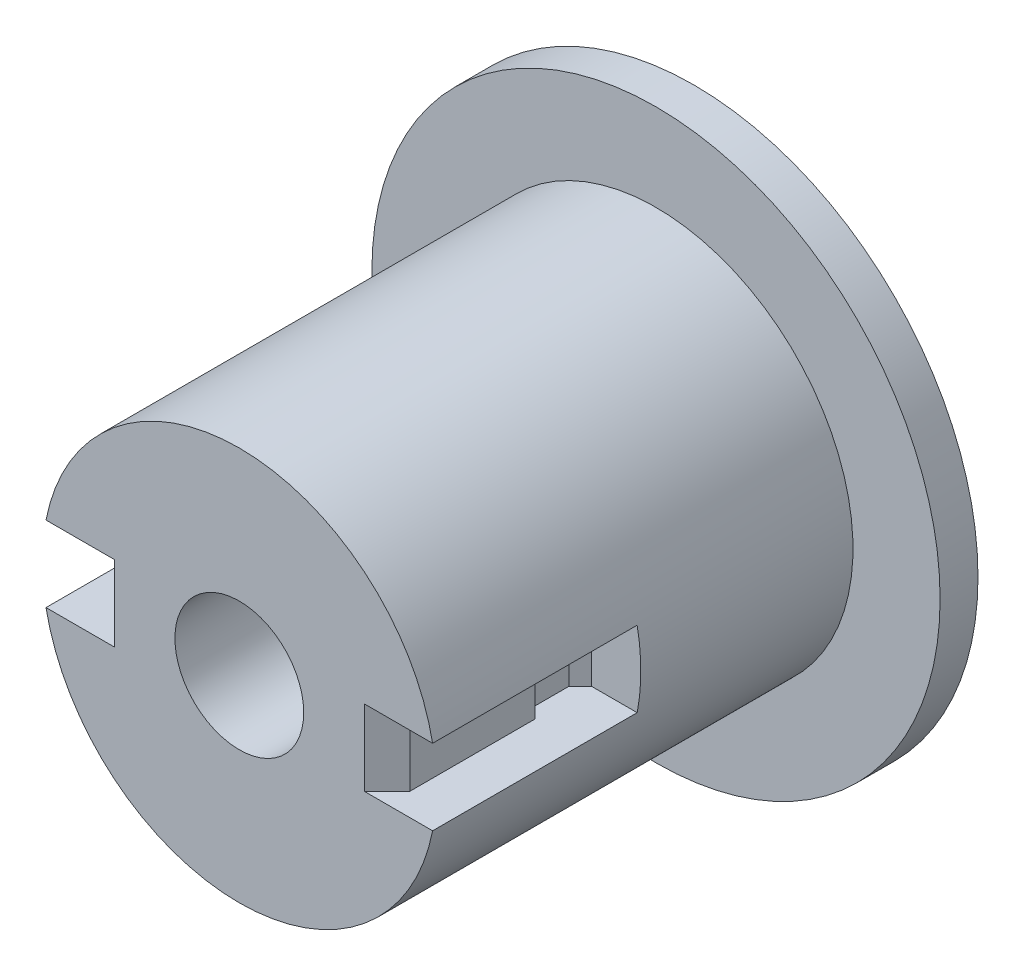
SolidWorks part; units mm, degrees
ref_plane "Front" through (0, 0, 0) normal (0, 0, 1) x (1, 0, 0)
ref_plane "Top" through (0, 0, 0) normal (0, 1, 0) x (1, 0, 0)
ref_plane "Right" through (0, 0, 0) normal (1, 0, 0) x (0, 0, -1)
sketch "Axle base sketch" plane through (0, 0, 0) normal (0, 0, 1) x (1, 0, 0)
  circle A0 centre (0, 0) radius 26
  dimension "D1" = 52
extrude "Axle" add sketch "Axle base sketch" along normal blind 55
sketch "Guard base sketch" plane through (0, 0, 0) normal (0, 0, -1) x (-1, 0, 0)
  circle A0 centre (0, 0) radius 37.5
  dimension "D1" = 75
extrude "Guard base" add sketch "Guard base sketch" along normal blind 5
sketch "Inner axle base sketch" plane through (0, 0, 55) normal (0, 0, 1) x (1, 0, 0)
  circle A0 centre (0, 0) radius 8.5
  dimension "D1" = 17
extrude "Inner axle hole" cut sketch "Inner axle base sketch" against normal through all
sketch "Coupling tooth base sketch" plane through (0, 0, 0) normal (0, 1, 0) x (1, 0, 0)
  line L0 (16.5, -55) -> (26, -55)
  line L1 (26, -55) -> (26, -28)
  line L2 (26, -55) -> (26, 0) construction
  line L3 (26, -28) -> (19.5, -28)
  line L5 (18, -34) -> (19.5, -35.5)
  line L6 (19.5, -35.5) -> (19.5, -52)
  line L7 (19.5, -52) -> (16.5, -55)
  line L9 (19.5, -28) -> (18, -29.5)
  line L10 (18, -29.5) -> (18, -34)
  dimension "D1" = 9.5
  dimension "D2" = 1.5
  dimension "D3" = 8
  dimension "D4" = 27
  dimension "D5" = 7.5
  dimension "D7" = 135
  dimension "D8" = 135
extrude "Coupling tooth room" cut sketch "Coupling tooth base sketch" against normal blind 5 and the other way blind 5 contours L9 L10 L5 L6 L7 L0 L1 L3 region at (22.4613, 0, 41.3333)
mirror "Coupling teeth" about plane through (0, 0, 0) normal (1, 0, 0) of "Coupling tooth room"
equation "\"53_55_spool_inner_diameter\"=53"
equation "\"D1@Axle base sketch\"=\"53_55_spool_inner_diameter\"-\"spool_inner_diameter_room\""
equation "\"large_inner_axle_diameter\"=20"
equation "\"small_inner_axle_diameter\"=17"
equation "\"guard_thickness\"=5"
equation "\"spool_inner_diameter_room\"=1"
equation "\"53_55_spool_thickness\"=55"
equation "\"53_55_guard_diameter\"=75"
equation "\"53_55_coupling_tooth_height\"=27"
equation "\"53_55_coupling_tooth_thickness_total\"=8"
equation "\"53_55_coupling_tooth_protrusion\"=1.5"
equation "\"53_55_coupling_tooth_head_height\"=7.5"
equation "\"53_55_coupling_tooth_depth\"=10"
equation "\"D1@Guard base sketch\"=\"53_55_guard_diameter\""
equation "\"D1@Guard base\"=\"guard_thickness\""
equation "\"D1@Axle\"=\"53_55_spool_thickness\""
equation "\"D1@Inner axle base sketch\"=\"small_inner_axle_diameter\""
equation "\"D4@Coupling tooth base sketch\"=\"53_55_coupling_tooth_height\""
equation "\"D3@Coupling tooth base sketch\"=\"53_55_coupling_tooth_thickness_total\""
equation "\"D5@Coupling tooth base sketch\"=\"53_55_coupling_tooth_head_height\""
equation "\"53_55_coupling_tooth_base_thickness\"=9.5"
equation "\"D1@Coupling tooth base sketch\"=\"53_55_coupling_tooth_base_thickness\""
equation "\"D2@Coupling tooth base sketch\"=\"53_55_coupling_tooth_protrusion\""
equation "\"D1@Coupling tooth room\"=\"53_55_coupling_tooth_depth\"/2"
equation "\"D2@Coupling tooth room\"=\"53_55_coupling_tooth_depth\"/2"
